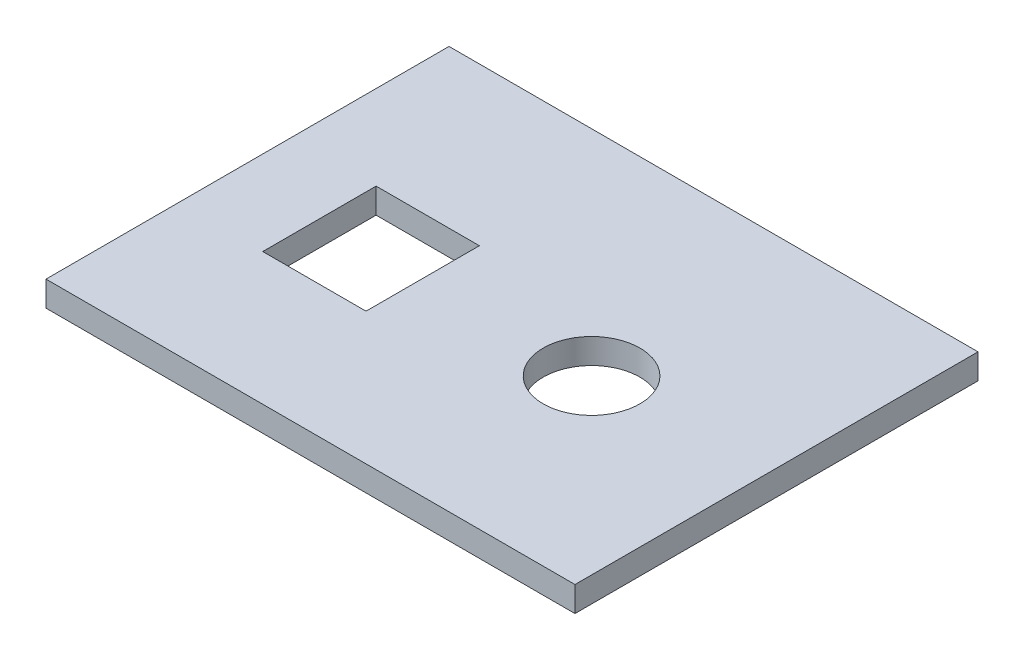
SolidWorks part; units mm, degrees
ref_plane "Front Plane" through (0, 0, 0) normal (0, 0, 1) x (1, 0, 0)
ref_plane "Top Plane" through (0, 0, 0) normal (0, 1, 0) x (1, 0, 0)
ref_plane "Right Plane" through (0, 0, 0) normal (1, 0, 0) x (0, 0, -1)
sketch "Sketch2" plane through (0, 0, 0) normal (0, 1, 0) x (1, 0, 0)
  line L1 (110, 85) -> (-100, 85)
  line L2 (110, 85) -> (110, -75)
  line L3 (110, -75) -> (-100, -75)
  line L4 (-100, 85) -> (-100, -75)
  line L5 (110, 85) -> (-100, -75) construction
  line L6 (110, -75) -> (-100, 85) construction
  point P0 (5, 5)
  dimension "D1" = 160
  dimension "D2" = 210
extrude "Boss-Extrude1" add sketch "Sketch2" along normal blind 10 contours L4 L3 L2 L1
sketch "Sketch3" plane through (0, 0, 0) normal (0, 1, 0) x (1, 0, 0)
  line L0 (0, 0) -> (22.385, 0) construction
  line L1 (0, 0) -> (-25.4527, 0) construction
  line L6 (-66.4527, -22.5) -> (-25.4527, -22.5)
  line L7 (-66.4527, -22.5) -> (-66.4527, 22.5)
  line L8 (-25.4527, -22.5) -> (-25.4527, 22.5)
  line L9 (-66.4527, 22.5) -> (-25.4527, 22.5)
  line L10 (-66.4527, -22.5) -> (-25.4527, 22.5) construction
  line L11 (-25.4527, -22.5) -> (-66.4527, 22.5) construction
  circle A1 centre (41.585, 0) radius 19.2
  point P7 (-45.9527, 0)
  dimension "D1" = 38.4
  dimension "D2" = 41
  dimension "D3" = 45
extrude "Cut-Extrude2" cut sketch "Sketch3" against normal blind 22 and the other way blind 15
